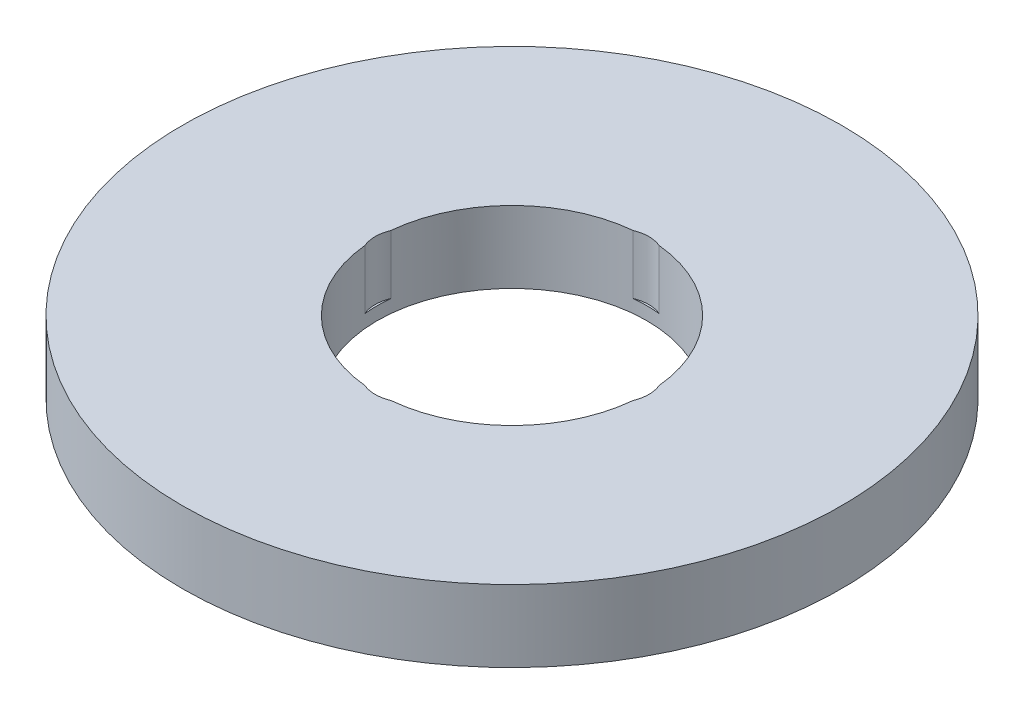
SolidWorks part; units mm, degrees
ref_plane "Front Plane" through (0, 0, 0) normal (0, 0, 1) x (1, 0, 0)
ref_plane "Top Plane" through (0, 0, 0) normal (0, 1, 0) x (1, 0, 0)
ref_plane "Right Plane" through (0, 0, 0) normal (1, 0, 0) x (0, 0, -1)
sketch "Sketch1" plane through (0, 0, 0) normal (0, 1, 0) x (1, 0, 0)
  circle A0 centre (0, 0) radius 55
  dimension "FLANGE_OD" = 110
extrude "Boss-Extrude1" add sketch "Sketch1" along normal blind 12
sketch "Sketch2" plane through (0, 0, 0) normal (0, 1, 0) x (1, 0, 0)
  circle A0 centre (0, 0) radius 22.5
  dimension "BORE_D" = 45
extrude "Cut-Extrude1" cut sketch "Sketch2" along normal through all
sketch "Sketch3" plane through (0, 12, 0) normal (0, 1, 0) x (1, 0, 0)
  circle A0 centre (0, 0) radius 17.242 construction
  circle A1 centre (-17.242, 0) radius 5.5898
  dimension "BOLT_D" = 11.1796
  dimension "BOLT_PCD" = 34.4841
extrude "Cut-Extrude2" cut sketch "Sketch3" against normal blind 9.8329
pattern_circular "CirPattern1" count 4 over 360 about axis through (0, 0, 0) along (0, 1, 0) of "Cut-Extrude2"
